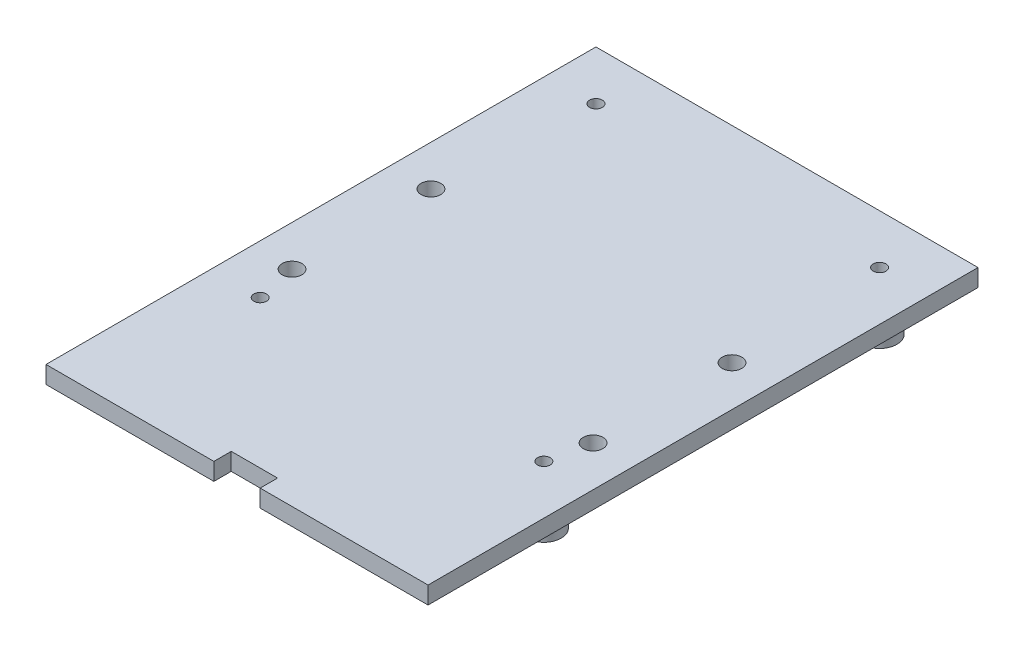
SolidWorks part; units mm, degrees
ref_plane "Front Plane" through (0, 0, 0) normal (0, 0, 1) x (1, 0, 0)
ref_plane "Top Plane" through (0, 0, 0) normal (0, 1, 0) x (1, 0, 0)
ref_plane "Right Plane" through (0, 0, 0) normal (1, 0, 0) x (0, 0, -1)
sketch "Sketch1" plane through (0, 0, 0) normal (0, 1, 0) x (1, 0, 0)
  line L1 (-131, 47.5) -> (-65, 47.5)
  line L2 (-131, 47.5) -> (-131, -47.5)
  line L3 (-131, -47.5) -> (-65, -47.5)
  line L4 (-65, 47.5) -> (-65, -47.5)
extrude "Cradle Base" add sketch "Sketch1" against normal blind 3
sketch "Sketch2" plane through (0, 0, 0) normal (0, 1, 0) x (1, 0, 0)
  circle A0 centre (-122.5, 39) radius 3
  circle A1 centre (-122.5, -19) radius 3
  circle A2 centre (-73.5, 39) radius 3
  circle A3 centre (-73.5, -19) radius 3
extrude "Standoffs" add sketch "Sketch2" against normal blind 10
sketch "Sketch3" plane through (0, 0, 0) normal (0, 1, 0) x (1, 0, 0)
  circle A0 centre (-122.5, 39) radius 1.1
  circle A1 centre (-122.5, -19) radius 1.1
  circle A2 centre (-73.5, 39) radius 1.1
  circle A3 centre (-73.5, -19) radius 1.1
  circle A4 centre (-124, 12) radius 1.7
  circle A5 centre (-124, -12) radius 1.7
  circle A6 centre (-72, -12) radius 1.7
  circle A7 centre (-72, 12) radius 1.7
extrude "Pilot and Bolt Holes" cut sketch "Sketch3" against normal through all and the other way through all
sketch "Sketch4" plane through (0, 0, 0) normal (0, 1, 0) x (1, 0, 0)
  line L1 (-102, -44.5) -> (-94, -44.5)
  line L2 (-102, -44.5) -> (-102, -48.5)
  line L3 (-102, -48.5) -> (-94, -48.5)
  line L4 (-94, -44.5) -> (-94, -48.5)
extrude "USB End Notch" cut sketch "Sketch4" against normal through all and the other way through all
equation "\"BaseT\" = 3.0"
equation "\"StandH\" = 7.0"
equation "\"StandD\" = 6.0"
equation "\"PilotD\" = 2.2"
equation "\"BoltD\" = 3.4"
equation "\"PiCX\" = -98.0"
equation "\"PiCZ\" = -10.0"
equation "\"HoleL\" = 58.0"
equation "\"HoleW\" = 49.0"
